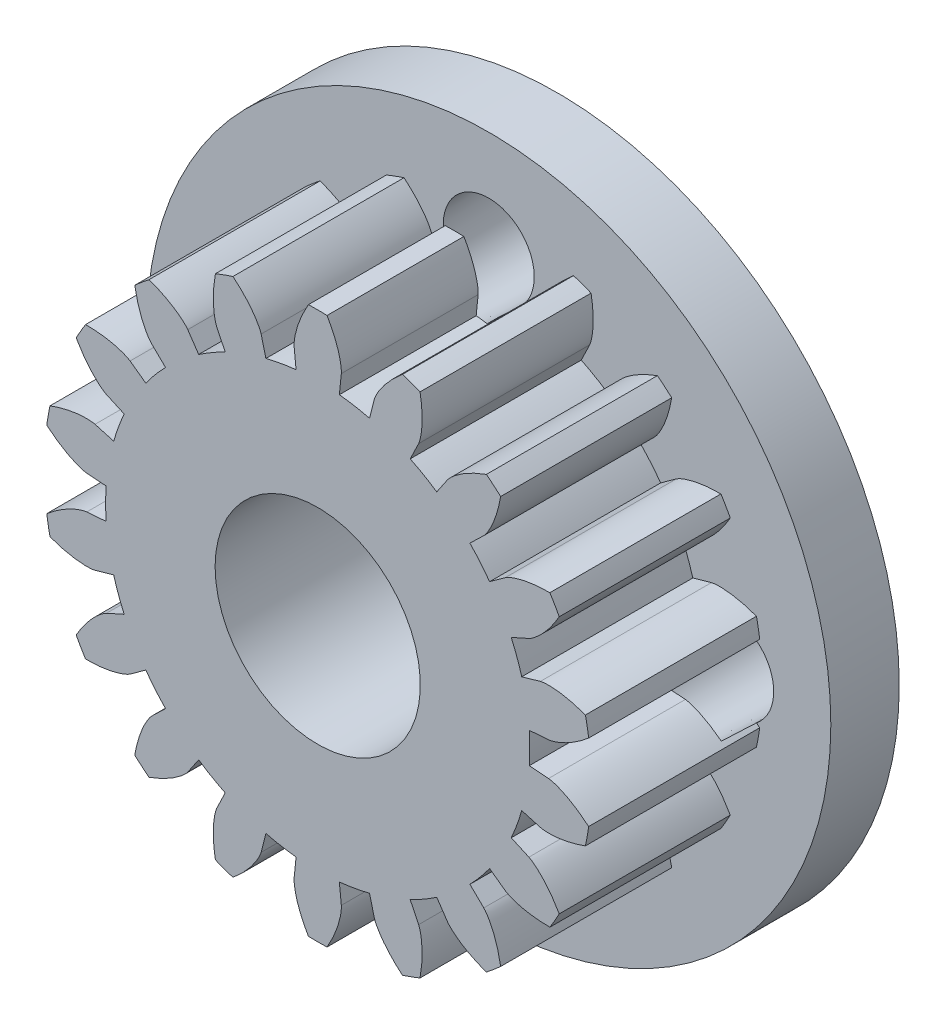
SolidWorks part; units mm, degrees
ref_plane "Front Plane" through (0, 0, 0) normal (0, 0, 1) x (1, 0, 0)
ref_plane "Top Plane" through (0, 0, 0) normal (0, 1, 0) x (1, 0, 0)
ref_plane "Right Plane" through (0, 0, 0) normal (1, 0, 0) x (0, 0, -1)
sketch "Sketch1" plane through (0, 0, 0) normal (0, 0, 1) x (1, 0, 0)
  circle A0 centre (0, 0) radius 10
  dimension "D1" = 20
extrude "Boss-Extrude1" add sketch "Sketch1" along normal blind 2
sketch "Sketch2" plane through (0, 0, 2) normal (0, 0, 1) x (1, 0, 0)
  line L0 (6.749, 0.4894) -> (6.1838, 0.4484)
  line L2 (6.7483, -0.4893) -> (6.1838, -0.4484)
  line L3 (6.5094, -1.8484) -> (5.9642, -1.6936)
  line L4 (6.174, -2.7678) -> (5.6575, -2.5363)
  line L5 (5.4846, -3.9633) -> (5.0253, -3.6313)
  line L6 (4.855, -4.7125) -> (4.4488, -4.3183)
  line L7 (3.7983, -5.6001) -> (3.4802, -5.1311)
  line L8 (2.9504, -6.0888) -> (2.7036, -5.5795)
  line L9 (1.6539, -6.5615) -> (1.5154, -6.012)
  line L10 (0.69, -6.7307) -> (0.6322, -6.1677)
  line L11 (-0.69, -6.7315) -> (-0.6322, -6.1677)
  line L12 (-1.6537, -6.5608) -> (-1.5154, -6.012)
  line L13 (-2.9507, -6.0895) -> (-2.7035, -5.5795)
  line L14 (-3.7979, -5.5995) -> (-3.4802, -5.1311)
  line L15 (-4.8555, -4.7131) -> (-4.4488, -4.3183)
  line L16 (-5.484, -3.9629) -> (-5.0252, -3.6314)
  line L17 (-6.1746, -2.7682) -> (-5.6575, -2.5363)
  line L18 (-6.5087, -1.8483) -> (-5.9642, -1.6936)
  line L19 (-6.749, -0.4894) -> (-6.1838, -0.4484)
  line L20 (-6.7483, 0.4893) -> (-6.1838, 0.4484)
  line L21 (-6.5094, 1.8484) -> (-5.9642, 1.6936)
  line L22 (-6.174, 2.7678) -> (-5.6575, 2.5363)
  line L23 (-5.4846, 3.9633) -> (-5.0253, 3.6313)
  line L24 (-4.855, 4.7125) -> (-4.4488, 4.3183)
  line L25 (-3.7983, 5.6001) -> (-3.4802, 5.1311)
  line L26 (-2.9504, 6.0888) -> (-2.7036, 5.5795)
  line L27 (-1.6539, 6.5615) -> (-1.5154, 6.012)
  line L28 (-0.69, 6.7307) -> (-0.6322, 6.1677)
  line L29 (0.69, 6.7315) -> (0.6322, 6.1677)
  line L30 (1.6537, 6.5608) -> (1.5154, 6.012)
  line L31 (2.9507, 6.0895) -> (2.7035, 5.5795)
  line L32 (3.7979, 5.5995) -> (3.4802, 5.1311)
  line L33 (4.8555, 4.7131) -> (4.4488, 4.3183)
  line L34 (5.484, 3.9629) -> (5.0252, 3.6314)
  line L35 (6.1746, 2.7682) -> (5.6575, 2.5363)
  line L36 (6.5087, 1.8483) -> (5.9642, 1.6936)
  arc A0 (6.1838, -0.4484) -> (6.1838, 0.4484) centre (0, 0) ccw
  arc A1 (6.1838, 0.4484) -> (6.1838, -0.4484) centre (0, 0) ccw construction
  arc A2 (2.9913, 7.4194) -> (2.4781, 7.6062) centre (0, 0) ccw
  arc A3 (5.6575, -2.5363) -> (5.9642, -1.6936) centre (0, 0) ccw
  arc A4 (4.4488, -4.3183) -> (5.0253, -3.6313) centre (0, 0) ccw
  arc A5 (2.7036, -5.5795) -> (3.4802, -5.1311) centre (0, 0) ccw
  arc A6 (0.6322, -6.1677) -> (1.5154, -6.012) centre (0, 0) ccw
  arc A7 (-1.5154, -6.012) -> (-0.6322, -6.1677) centre (0, 0) ccw
  arc A8 (-3.4802, -5.1311) -> (-2.7035, -5.5795) centre (0, 0) ccw
  arc A9 (-5.0252, -3.6314) -> (-4.4488, -4.3183) centre (0, 0) ccw
  arc A10 (-5.9642, -1.6936) -> (-5.6575, -2.5363) centre (0, 0) ccw
  arc A11 (-6.1838, 0.4484) -> (-6.1838, -0.4484) centre (0, 0) ccw
  arc A12 (-5.6575, 2.5363) -> (-5.9642, 1.6936) centre (0, 0) ccw
  arc A13 (-4.4488, 4.3183) -> (-5.0253, 3.6313) centre (0, 0) ccw
  arc A14 (-2.7036, 5.5795) -> (-3.4802, 5.1311) centre (0, 0) ccw
  arc A15 (-0.6322, 6.1677) -> (-1.5154, 6.012) centre (0, 0) ccw
  arc A16 (1.5154, 6.012) -> (0.6322, 6.1677) centre (0, 0) ccw
  arc A17 (3.4802, 5.1311) -> (2.7035, 5.5795) centre (0, 0) ccw
  arc A18 (5.0252, 3.6314) -> (4.4488, 4.3183) centre (0, 0) ccw
  arc A19 (5.9642, 1.6936) -> (5.6575, 2.5363) centre (0, 0) ccw
  arc A20 (4.9301, 6.2999) -> (2.9913, 7.4194) centre (0, 0) ccw construction
  arc A21 (6.7875, 4.2338) -> (5.3484, 5.9489) centre (0, 0) ccw construction
  arc A22 (5.3484, 5.9489) -> (4.9301, 6.2999) centre (0, 0) ccw
  arc A23 (7.8262, 1.657) -> (7.0605, 3.7608) centre (0, 0) ccw construction
  arc A24 (7.0605, 3.7608) -> (6.7875, 4.2338) centre (0, 0) ccw
  arc A25 (7.9209, -1.1196) -> (7.921, 1.1192) centre (0, 0) ccw construction
  arc A26 (7.921, 1.1192) -> (7.8262, 1.657) centre (0, 0) ccw
  arc A27 (7.0603, -3.7612) -> (7.8261, -1.6575) centre (0, 0) ccw construction
  arc A28 (7.8261, -1.6575) -> (7.9209, -1.1196) centre (0, 0) ccw
  arc A29 (5.3481, -5.9492) -> (6.7872, -4.2342) centre (0, 0) ccw construction
  arc A30 (6.7872, -4.2342) -> (7.0603, -3.7612) centre (0, 0) ccw
  arc A31 (2.9908, -7.4196) -> (4.9297, -6.3002) centre (0, 0) ccw construction
  arc A32 (4.9297, -6.3002) -> (5.3481, -5.9492) centre (0, 0) ccw
  arc A33 (0.2728, -7.995) -> (2.4776, -7.6063) centre (0, 0) ccw construction
  arc A34 (2.4776, -7.6063) -> (2.9908, -7.4196) centre (0, 0) ccw
  arc A35 (-2.4781, -7.6062) -> (-0.2733, -7.995) centre (0, 0) ccw construction
  arc A36 (-0.2733, -7.995) -> (0.2728, -7.995) centre (0, 0) ccw
  arc A37 (-4.9301, -6.2999) -> (-2.9913, -7.4194) centre (0, 0) ccw construction
  arc A38 (-2.9913, -7.4194) -> (-2.4781, -7.6062) centre (0, 0) ccw
  arc A39 (-6.7875, -4.2338) -> (-5.3484, -5.9489) centre (0, 0) ccw construction
  arc A40 (-5.3484, -5.9489) -> (-4.9301, -6.2999) centre (0, 0) ccw
  arc A41 (-7.8262, -1.657) -> (-7.0605, -3.7608) centre (0, 0) ccw construction
  arc A42 (-7.0605, -3.7608) -> (-6.7875, -4.2338) centre (0, 0) ccw
  arc A43 (-7.9209, 1.1196) -> (-7.921, -1.1192) centre (0, 0) ccw construction
  arc A44 (-7.921, -1.1192) -> (-7.8262, -1.657) centre (0, 0) ccw
  arc A45 (-7.0603, 3.7612) -> (-7.8261, 1.6575) centre (0, 0) ccw construction
  arc A46 (-7.8261, 1.6575) -> (-7.9209, 1.1196) centre (0, 0) ccw
  arc A47 (-5.3481, 5.9492) -> (-6.7872, 4.2342) centre (0, 0) ccw construction
  arc A48 (-6.7872, 4.2342) -> (-7.0603, 3.7612) centre (0, 0) ccw
  arc A49 (-2.9908, 7.4196) -> (-4.9297, 6.3002) centre (0, 0) ccw construction
  arc A50 (-4.9297, 6.3002) -> (-5.3481, 5.9492) centre (0, 0) ccw
  arc A51 (-0.2728, 7.995) -> (-2.4776, 7.6063) centre (0, 0) ccw construction
  arc A52 (-2.4776, 7.6063) -> (-2.9908, 7.4196) centre (0, 0) ccw
  arc A53 (2.4781, 7.6062) -> (0.2733, 7.995) centre (0, 0) ccw construction
  arc A54 (0.2733, 7.995) -> (-0.2728, 7.995) centre (0, 0) ccw
  spline S0 degree 4 poles (6.749, 0.4894) (6.7546, 0.4899) (6.765, 0.4912) (6.7821, 0.4939) (6.8156, 0.5002) (6.8532, 0.5091) (6.8954, 0.5207) (6.9405, 0.5347) (6.9788, 0.5477) (7.0169, 0.5615) (7.0547, 0.5761) (7.1002, 0.5948) (7.1544, 0.6185) (7.2173, 0.6482) (7.288, 0.6841) (7.3594, 0.7231) (7.429, 0.7635) (7.4986, 0.8065) (7.5654, 0.8498) (7.6341, 0.897) (7.697, 0.9417) (7.7666, 0.9943) (7.8225, 1.0375) (7.8951, 1.0972) (7.9377, 1.1332) (7.9872, 1.1762) (8.009, 1.1958) (8.0224, 1.2079) knots 0 0 0 0 0 0.015084 0.028532 0.04661 0.092111 0.119476 0.146842 0.174209 0.201575 0.228941 0.256307 0.307035 0.361767 0.4165 0.471232 0.525964 0.580697 0.635429 0.690161 0.744894 0.799626 0.854358 0.909091 0.954545 1 1 1 1 1 construction
  spline S1 degree 4 poles (6.749, 0.4894) (6.7546, 0.4899) (6.765, 0.4912) (6.7821, 0.4939) (6.8156, 0.5002) (6.8532, 0.5091) (6.8954, 0.5207) (6.9405, 0.5347) (6.9788, 0.5477) (7.0169, 0.5615) (7.0547, 0.5761) (7.1002, 0.5948) (7.1544, 0.6185) (7.2173, 0.6482) (7.288, 0.6841) (7.3594, 0.7231) (7.429, 0.7635) (7.4986, 0.8065) (7.5654, 0.8498) (7.6341, 0.897) (7.697, 0.9417) (7.7666, 0.9943) (7.8225, 1.0375) (7.8794, 1.0842) (7.907, 1.1073) (7.921, 1.1192) knots 0 0 0 0 0 0.015084 0.028532 0.04661 0.092111 0.119476 0.146842 0.174209 0.201575 0.228941 0.256307 0.307035 0.361767 0.4165 0.471232 0.525964 0.580697 0.635429 0.690161 0.744894 0.799626 0.854358 0.909091 0.909091 0.909091 0.909091 0.909091
  spline S2 degree 4 poles (6.7483, -0.4893) (6.7539, -0.4898) (6.7643, -0.4911) (6.7814, -0.4938) (6.8149, -0.5002) (6.8525, -0.509) (6.8948, -0.5206) (6.9399, -0.5346) (6.9783, -0.5476) (7.0164, -0.5615) (7.0541, -0.5761) (7.0997, -0.5948) (7.1539, -0.6185) (7.2169, -0.6482) (7.2876, -0.6841) (7.359, -0.7232) (7.4287, -0.7636) (7.4983, -0.8067) (7.5652, -0.85) (7.6339, -0.8972) (7.6968, -0.942) (7.7664, -0.9947) (7.8224, -1.0379) (7.8951, -1.0976) (7.9377, -1.1337) (7.9872, -1.1767) (8.009, -1.1963) (8.0224, -1.2084) knots 0 0 0 0 0 0.015084 0.028532 0.04661 0.092111 0.119476 0.146842 0.174209 0.201575 0.228941 0.256307 0.307035 0.361767 0.4165 0.471232 0.525964 0.580697 0.635429 0.690161 0.744894 0.799626 0.854358 0.909091 0.954545 1 1 1 1 1 construction
  spline S3 degree 4 poles (6.7483, -0.4893) (6.7539, -0.4898) (6.7643, -0.4911) (6.7814, -0.4938) (6.8149, -0.5002) (6.8525, -0.509) (6.8948, -0.5206) (6.9399, -0.5346) (6.9783, -0.5476) (7.0164, -0.5615) (7.0541, -0.5761) (7.0997, -0.5948) (7.1539, -0.6185) (7.2169, -0.6482) (7.2876, -0.6841) (7.359, -0.7232) (7.4287, -0.7636) (7.4983, -0.8067) (7.5652, -0.85) (7.6339, -0.8972) (7.6968, -0.942) (7.7664, -0.9947) (7.8224, -1.0379) (7.8793, -1.0847) (7.9069, -1.1077) (7.9209, -1.1196) knots 0 0 0 0 0 0.015084 0.028532 0.04661 0.092111 0.119476 0.146842 0.174209 0.201575 0.228941 0.256307 0.307035 0.361767 0.4165 0.471232 0.525964 0.580697 0.635429 0.690161 0.744894 0.799626 0.854358 0.909091 0.909091 0.909091 0.909091 0.909091
  spline S4 degree 4 poles (6.5094, -1.8484) (6.5148, -1.8499) (6.5251, -1.8522) (6.542, -1.8555) (6.5756, -1.861) (6.614, -1.8655) (6.6576, -1.8691) (6.7048, -1.8713) (6.7453, -1.8723) (6.7858, -1.8723) (6.8263, -1.8715) (6.8754, -1.8695) (6.9345, -1.8657) (7.0037, -1.8594) (7.0825, -1.8498) (7.1629, -1.8376) (7.2421, -1.8234) (7.3222, -1.8068) (7.3998, -1.789) (7.4805, -1.7681) (7.5549, -1.7476) (7.6383, -1.722) (7.7056, -1.7005) (7.7943, -1.6693) (7.8466, -1.65) (7.9078, -1.6265) (7.935, -1.6155) (7.9517, -1.6088) knots 0 0 0 0 0 0.015084 0.028532 0.04661 0.092111 0.119476 0.146842 0.174209 0.201575 0.228941 0.256307 0.307035 0.361767 0.4165 0.471232 0.525964 0.580697 0.635429 0.690161 0.744894 0.799626 0.854358 0.909091 0.954545 1 1 1 1 1 construction
  spline S5 degree 4 poles (6.5094, -1.8484) (6.5148, -1.8499) (6.5251, -1.8522) (6.542, -1.8555) (6.5756, -1.861) (6.614, -1.8655) (6.6576, -1.8691) (6.7048, -1.8713) (6.7453, -1.8723) (6.7858, -1.8723) (6.8263, -1.8715) (6.8754, -1.8695) (6.9345, -1.8657) (7.0037, -1.8594) (7.0825, -1.8498) (7.1629, -1.8376) (7.2421, -1.8234) (7.3222, -1.8068) (7.3998, -1.789) (7.4805, -1.7681) (7.5549, -1.7476) (7.6383, -1.722) (7.7056, -1.7005) (7.775, -1.676) (7.8088, -1.6638) (7.8261, -1.6575) knots 0 0 0 0 0 0.015084 0.028532 0.04661 0.092111 0.119476 0.146842 0.174209 0.201575 0.228941 0.256307 0.307035 0.361767 0.4165 0.471232 0.525964 0.580697 0.635429 0.690161 0.744894 0.799626 0.854358 0.909091 0.909091 0.909091 0.909091 0.909091
  spline S6 degree 4 poles (6.174, -2.7678) (6.179, -2.7702) (6.1884, -2.775) (6.2036, -2.7834) (6.2328, -2.8008) (6.2652, -2.822) (6.3009, -2.8473) (6.3385, -2.876) (6.3701, -2.9013) (6.4012, -2.9273) (6.4317, -2.954) (6.4681, -2.9871) (6.511, -3.028) (6.5599, -3.0774) (6.6141, -3.1354) (6.6679, -3.1965) (6.7195, -3.2583) (6.7702, -3.3226) (6.8183, -3.3862) (6.8666, -3.454) (6.9105, -3.5177) (6.9579, -3.591) (6.9956, -3.6507) (7.0435, -3.7317) (7.0713, -3.7801) (7.103, -3.8375) (7.1168, -3.8634) (7.1253, -3.8793) knots 0 0 0 0 0 0.015084 0.028532 0.04661 0.092111 0.119476 0.146842 0.174209 0.201575 0.228941 0.256307 0.307035 0.361767 0.4165 0.471232 0.525964 0.580697 0.635429 0.690161 0.744894 0.799626 0.854358 0.909091 0.954545 1 1 1 1 1 construction
  spline S7 degree 4 poles (6.174, -2.7678) (6.179, -2.7702) (6.1884, -2.775) (6.2036, -2.7834) (6.2328, -2.8008) (6.2652, -2.822) (6.3009, -2.8473) (6.3385, -2.876) (6.3701, -2.9013) (6.4012, -2.9273) (6.4317, -2.954) (6.4681, -2.9871) (6.511, -3.028) (6.5599, -3.0774) (6.6141, -3.1354) (6.6679, -3.1965) (6.7195, -3.2583) (6.7702, -3.3226) (6.8183, -3.3862) (6.8666, -3.454) (6.9105, -3.5177) (6.9579, -3.591) (6.9956, -3.6507) (7.0331, -3.7141) (7.0512, -3.7452) (7.0603, -3.7612) knots 0 0 0 0 0 0.015084 0.028532 0.04661 0.092111 0.119476 0.146842 0.174209 0.201575 0.228941 0.256307 0.307035 0.361767 0.4165 0.471232 0.525964 0.580697 0.635429 0.690161 0.744894 0.799626 0.854358 0.909091 0.909091 0.909091 0.909091 0.909091
  spline S8 degree 4 poles (5.4846, -3.9633) (5.4892, -3.9665) (5.4981, -3.9722) (5.5128, -3.9811) (5.5426, -3.9978) (5.5771, -4.0152) (5.6169, -4.0334) (5.6604, -4.0517) (5.6981, -4.0664) (5.7362, -4.0802) (5.7745, -4.0933) (5.8214, -4.1083) (5.8782, -4.125) (5.9454, -4.1427) (6.0226, -4.1606) (6.1024, -4.1766) (6.1817, -4.1904) (6.2627, -4.2022) (6.3417, -4.212) (6.4246, -4.22) (6.5016, -4.2261) (6.5887, -4.2306) (6.6593, -4.2334) (6.7533, -4.2344) (6.8091, -4.2342) (6.8746, -4.233) (6.9039, -4.232) (6.9219, -4.2314) knots 0 0 0 0 0 0.015084 0.028532 0.04661 0.092111 0.119476 0.146842 0.174209 0.201575 0.228941 0.256307 0.307035 0.361767 0.4165 0.471232 0.525964 0.580697 0.635429 0.690161 0.744894 0.799626 0.854358 0.909091 0.954545 1 1 1 1 1 construction
  spline S9 degree 4 poles (5.4846, -3.9633) (5.4892, -3.9665) (5.4981, -3.9722) (5.5128, -3.9811) (5.5426, -3.9978) (5.5771, -4.0152) (5.6169, -4.0334) (5.6604, -4.0517) (5.6981, -4.0664) (5.7362, -4.0802) (5.7745, -4.0933) (5.8214, -4.1083) (5.8782, -4.125) (5.9454, -4.1427) (6.0226, -4.1606) (6.1024, -4.1766) (6.1817, -4.1904) (6.2627, -4.2022) (6.3417, -4.212) (6.4246, -4.22) (6.5016, -4.2261) (6.5887, -4.2306) (6.6593, -4.2334) (6.7329, -4.2342) (6.7688, -4.2343) (6.7872, -4.2342) knots 0 0 0 0 0 0.015084 0.028532 0.04661 0.092111 0.119476 0.146842 0.174209 0.201575 0.228941 0.256307 0.307035 0.361767 0.4165 0.471232 0.525964 0.580697 0.635429 0.690161 0.744894 0.799626 0.854358 0.909091 0.909091 0.909091 0.909091 0.909091
  spline S10 degree 4 poles (4.855, -4.7125) (4.8589, -4.7165) (4.8661, -4.7243) (4.8775, -4.7372) (4.899, -4.7637) (4.9222, -4.7946) (4.9471, -4.8307) (4.9726, -4.8704) (4.9937, -4.905) (5.0139, -4.9401) (5.0335, -4.9756) (5.0563, -5.0192) (5.0827, -5.0723) (5.1118, -5.1355) (5.1429, -5.2085) (5.1725, -5.2843) (5.1999, -5.36) (5.2255, -5.4378) (5.2489, -5.5139) (5.2712, -5.5943) (5.2906, -5.669) (5.3101, -5.7541) (5.3251, -5.8232) (5.3424, -5.9157) (5.3519, -5.9707) (5.3622, -6.0355) (5.3662, -6.0645) (5.3688, -6.0824) knots 0 0 0 0 0 0.015084 0.028532 0.04661 0.092111 0.119476 0.146842 0.174209 0.201575 0.228941 0.256307 0.307035 0.361767 0.4165 0.471232 0.525964 0.580697 0.635429 0.690161 0.744894 0.799626 0.854358 0.909091 0.954545 1 1 1 1 1 construction
  spline S11 degree 4 poles (4.855, -4.7125) (4.8589, -4.7165) (4.8661, -4.7243) (4.8775, -4.7372) (4.899, -4.7637) (4.9222, -4.7946) (4.9471, -4.8307) (4.9726, -4.8704) (4.9937, -4.905) (5.0139, -4.9401) (5.0335, -4.9756) (5.0563, -5.0192) (5.0827, -5.0723) (5.1118, -5.1355) (5.1429, -5.2085) (5.1725, -5.2843) (5.1999, -5.36) (5.2255, -5.4378) (5.2489, -5.5139) (5.2712, -5.5943) (5.2906, -5.669) (5.3101, -5.7541) (5.3251, -5.8232) (5.3387, -5.8956) (5.345, -5.931) (5.3481, -5.9492) knots 0 0 0 0 0 0.015084 0.028532 0.04661 0.092111 0.119476 0.146842 0.174209 0.201575 0.228941 0.256307 0.307035 0.361767 0.4165 0.471232 0.525964 0.580697 0.635429 0.690161 0.744894 0.799626 0.854358 0.909091 0.909091 0.909091 0.909091 0.909091
  spline S12 degree 4 poles (3.7983, -5.6001) (3.8015, -5.6047) (3.8079, -5.6131) (3.8187, -5.6265) (3.841, -5.6523) (3.8675, -5.6805) (3.8986, -5.7113) (3.9333, -5.7433) (3.9637, -5.77) (3.9947, -5.7961) (4.0263, -5.8215) (4.0652, -5.8515) (4.1128, -5.8866) (4.17, -5.9263) (4.2364, -5.9696) (4.3059, -6.0119) (4.3757, -6.052) (4.4478, -6.0907) (4.5186, -6.127) (4.5938, -6.1628) (4.664, -6.1949) (4.7444, -6.2289) (4.8098, -6.2557) (4.8978, -6.2888) (4.9502, -6.3077) (5.0123, -6.329) (5.0401, -6.3381) (5.0573, -6.3437) knots 0 0 0 0 0 0.015084 0.028532 0.04661 0.092111 0.119476 0.146842 0.174209 0.201575 0.228941 0.256307 0.307035 0.361767 0.4165 0.471232 0.525964 0.580697 0.635429 0.690161 0.744894 0.799626 0.854358 0.909091 0.954545 1 1 1 1 1 construction
  spline S13 degree 4 poles (3.7983, -5.6001) (3.8015, -5.6047) (3.8079, -5.6131) (3.8187, -5.6265) (3.841, -5.6523) (3.8675, -5.6805) (3.8986, -5.7113) (3.9333, -5.7433) (3.9637, -5.77) (3.9947, -5.7961) (4.0263, -5.8215) (4.0652, -5.8515) (4.1128, -5.8866) (4.17, -5.9263) (4.2364, -5.9696) (4.3059, -6.0119) (4.3757, -6.052) (4.4478, -6.0907) (4.5186, -6.127) (4.5938, -6.1628) (4.664, -6.1949) (4.7444, -6.2289) (4.8098, -6.2557) (4.8787, -6.2816) (4.9124, -6.294) (4.9297, -6.3002) knots 0 0 0 0 0 0.015084 0.028532 0.04661 0.092111 0.119476 0.146842 0.174209 0.201575 0.228941 0.256307 0.307035 0.361767 0.4165 0.471232 0.525964 0.580697 0.635429 0.690161 0.744894 0.799626 0.854358 0.909091 0.909091 0.909091 0.909091 0.909091
  spline S14 degree 4 poles (2.9504, -6.0888) (2.9528, -6.0939) (2.9569, -6.1037) (2.9631, -6.1197) (2.9743, -6.152) (2.9855, -6.189) (2.9965, -6.2313) (3.0069, -6.2774) (3.0149, -6.3172) (3.0219, -6.3571) (3.0282, -6.3971) (3.0347, -6.4459) (3.0413, -6.5047) (3.0471, -6.5741) (3.0513, -6.6533) (3.0532, -6.7347) (3.053, -6.8152) (3.0506, -6.8971) (3.0465, -6.9766) (3.0399, -7.0597) (3.0326, -7.1366) (3.0218, -7.2233) (3.0123, -7.2933) (2.997, -7.3861) (2.9871, -7.4411) (2.9745, -7.5055) (2.9684, -7.5342) (2.9647, -7.5518) knots 0 0 0 0 0 0.015084 0.028532 0.04661 0.092111 0.119476 0.146842 0.174209 0.201575 0.228941 0.256307 0.307035 0.361767 0.4165 0.471232 0.525964 0.580697 0.635429 0.690161 0.744894 0.799626 0.854358 0.909091 0.954545 1 1 1 1 1 construction
  spline S15 degree 4 poles (2.9504, -6.0888) (2.9528, -6.0939) (2.9569, -6.1037) (2.9631, -6.1197) (2.9743, -6.152) (2.9855, -6.189) (2.9965, -6.2313) (3.0069, -6.2774) (3.0149, -6.3172) (3.0219, -6.3571) (3.0282, -6.3971) (3.0347, -6.4459) (3.0413, -6.5047) (3.0471, -6.5741) (3.0513, -6.6533) (3.0532, -6.7347) (3.053, -6.8152) (3.0506, -6.8971) (3.0465, -6.9766) (3.0399, -7.0597) (3.0326, -7.1366) (3.0218, -7.2233) (3.0123, -7.2933) (3.0003, -7.366) (2.9941, -7.4014) (2.9908, -7.4196) knots 0 0 0 0 0 0.015084 0.028532 0.04661 0.092111 0.119476 0.146842 0.174209 0.201575 0.228941 0.256307 0.307035 0.361767 0.4165 0.471232 0.525964 0.580697 0.635429 0.690161 0.744894 0.799626 0.854358 0.909091 0.909091 0.909091 0.909091 0.909091
  spline S16 degree 4 poles (1.6539, -6.5615) (1.6554, -6.5669) (1.6585, -6.577) (1.664, -6.5933) (1.6762, -6.6252) (1.6914, -6.6607) (1.7101, -6.7002) (1.7318, -6.7422) (1.7512, -6.7777) (1.7714, -6.8128) (1.7924, -6.8474) (1.8187, -6.889) (1.8515, -6.9383) (1.8916, -6.9951) (1.9392, -7.0585) (1.99, -7.122) (2.0419, -7.1836) (2.0964, -7.2446) (2.1506, -7.3029) (2.209, -7.3623) (2.264, -7.4165) (2.3279, -7.4759) (2.3801, -7.5235) (2.4515, -7.5847) (2.4943, -7.6204) (2.5453, -7.6616) (2.5684, -7.6797) (2.5826, -7.6908) knots 0 0 0 0 0 0.015084 0.028532 0.04661 0.092111 0.119476 0.146842 0.174209 0.201575 0.228941 0.256307 0.307035 0.361767 0.4165 0.471232 0.525964 0.580697 0.635429 0.690161 0.744894 0.799626 0.854358 0.909091 0.954545 1 1 1 1 1 construction
  spline S17 degree 4 poles (1.6539, -6.5615) (1.6554, -6.5669) (1.6585, -6.577) (1.664, -6.5933) (1.6762, -6.6252) (1.6914, -6.6607) (1.7101, -6.7002) (1.7318, -6.7422) (1.7512, -6.7777) (1.7714, -6.8128) (1.7924, -6.8474) (1.8187, -6.889) (1.8515, -6.9383) (1.8916, -6.9951) (1.9392, -7.0585) (1.99, -7.122) (2.0419, -7.1836) (2.0964, -7.2446) (2.1506, -7.3029) (2.209, -7.3623) (2.264, -7.4165) (2.3279, -7.4759) (2.3801, -7.5235) (2.436, -7.5714) (2.4635, -7.5946) (2.4776, -7.6063) knots 0 0 0 0 0 0.015084 0.028532 0.04661 0.092111 0.119476 0.146842 0.174209 0.201575 0.228941 0.256307 0.307035 0.361767 0.4165 0.471232 0.525964 0.580697 0.635429 0.690161 0.744894 0.799626 0.854358 0.909091 0.909091 0.909091 0.909091 0.909091
  spline S18 degree 4 poles (0.69, -6.7307) (0.6905, -6.7363) (0.691, -6.7469) (0.6913, -6.7641) (0.6908, -6.7982) (0.6887, -6.8368) (0.6846, -6.8804) (0.6786, -6.9273) (0.6725, -6.9673) (0.6654, -7.0073) (0.6576, -7.047) (0.6471, -7.0951) (0.6332, -7.1527) (0.6148, -7.2198) (0.5917, -7.2957) (0.5657, -7.3728) (0.538, -7.4484) (0.5076, -7.5245) (0.4766, -7.5979) (0.442, -7.6737) (0.4088, -7.7435) (0.3691, -7.8212) (0.3362, -7.8837) (0.29, -7.9657) (0.2619, -8.0139) (0.2281, -8.0702) (0.2126, -8.0951) (0.203, -8.1104) knots 0 0 0 0 0 0.015084 0.028532 0.04661 0.092111 0.119476 0.146842 0.174209 0.201575 0.228941 0.256307 0.307035 0.361767 0.4165 0.471232 0.525964 0.580697 0.635429 0.690161 0.744894 0.799626 0.854358 0.909091 0.954545 1 1 1 1 1 construction
  spline S19 degree 4 poles (0.69, -6.7307) (0.6905, -6.7363) (0.691, -6.7469) (0.6913, -6.7641) (0.6908, -6.7982) (0.6887, -6.8368) (0.6846, -6.8804) (0.6786, -6.9273) (0.6725, -6.9673) (0.6654, -7.0073) (0.6576, -7.047) (0.6471, -7.0951) (0.6332, -7.1527) (0.6148, -7.2198) (0.5917, -7.2957) (0.5657, -7.3728) (0.538, -7.4484) (0.5076, -7.5245) (0.4766, -7.5979) (0.442, -7.6737) (0.4088, -7.7435) (0.3691, -7.8212) (0.3362, -7.8837) (0.3, -7.9479) (0.2821, -7.9791) (0.2728, -7.995) knots 0 0 0 0 0 0.015084 0.028532 0.04661 0.092111 0.119476 0.146842 0.174209 0.201575 0.228941 0.256307 0.307035 0.361767 0.4165 0.471232 0.525964 0.580697 0.635429 0.690161 0.744894 0.799626 0.854358 0.909091 0.909091 0.909091 0.909091 0.909091
  spline S20 degree 4 poles (-0.69, -6.7315) (-0.6905, -6.737) (-0.691, -6.7476) (-0.6913, -6.7648) (-0.6909, -6.7989) (-0.6887, -6.8375) (-0.6846, -6.8811) (-0.6786, -6.9279) (-0.6725, -6.9679) (-0.6655, -7.0078) (-0.6577, -7.0475) (-0.6472, -7.0956) (-0.6332, -7.1531) (-0.615, -7.2202) (-0.5919, -7.2961) (-0.5658, -7.3731) (-0.5382, -7.4487) (-0.5079, -7.5247) (-0.4769, -7.5981) (-0.4423, -7.6738) (-0.4092, -7.7436) (-0.3694, -7.8213) (-0.3366, -7.8838) (-0.2905, -7.9657) (-0.2624, -8.0139) (-0.2286, -8.0701) (-0.2131, -8.095) (-0.2036, -8.1103) knots 0 0 0 0 0 0.015084 0.028532 0.04661 0.092111 0.119476 0.146842 0.174209 0.201575 0.228941 0.256307 0.307035 0.361767 0.4165 0.471232 0.525964 0.580697 0.635429 0.690161 0.744894 0.799626 0.854358 0.909091 0.954545 1 1 1 1 1 construction
  spline S21 degree 4 poles (-0.69, -6.7315) (-0.6905, -6.737) (-0.691, -6.7476) (-0.6913, -6.7648) (-0.6909, -6.7989) (-0.6887, -6.8375) (-0.6846, -6.8811) (-0.6786, -6.9279) (-0.6725, -6.9679) (-0.6655, -7.0078) (-0.6577, -7.0475) (-0.6472, -7.0956) (-0.6332, -7.1531) (-0.615, -7.2202) (-0.5919, -7.2961) (-0.5658, -7.3731) (-0.5382, -7.4487) (-0.5079, -7.5247) (-0.4769, -7.5981) (-0.4423, -7.6738) (-0.4092, -7.7436) (-0.3694, -7.8213) (-0.3366, -7.8838) (-0.3005, -7.9479) (-0.2826, -7.9791) (-0.2733, -7.995) knots 0 0 0 0 0 0.015084 0.028532 0.04661 0.092111 0.119476 0.146842 0.174209 0.201575 0.228941 0.256307 0.307035 0.361767 0.4165 0.471232 0.525964 0.580697 0.635429 0.690161 0.744894 0.799626 0.854358 0.909091 0.909091 0.909091 0.909091 0.909091
  spline S22 degree 4 poles (-1.6537, -6.5608) (-1.6551, -6.5662) (-1.6583, -6.5763) (-1.6638, -6.5926) (-1.6759, -6.6245) (-1.6912, -6.66) (-1.7099, -6.6996) (-1.7316, -6.7416) (-1.7511, -6.7772) (-1.7713, -6.8123) (-1.7923, -6.8469) (-1.8186, -6.8885) (-1.8514, -6.9378) (-1.8915, -6.9947) (-1.9392, -7.0581) (-1.9901, -7.1216) (-2.042, -7.1832) (-2.0965, -7.2443) (-2.1507, -7.3027) (-2.2092, -7.3621) (-2.2642, -7.4163) (-2.3282, -7.4757) (-2.3805, -7.5233) (-2.4519, -7.5845) (-2.4948, -7.6202) (-2.5458, -7.6615) (-2.5689, -7.6796) (-2.5831, -7.6907) knots 0 0 0 0 0 0.015084 0.028532 0.04661 0.092111 0.119476 0.146842 0.174209 0.201575 0.228941 0.256307 0.307035 0.361767 0.4165 0.471232 0.525964 0.580697 0.635429 0.690161 0.744894 0.799626 0.854358 0.909091 0.954545 1 1 1 1 1 construction
  spline S23 degree 4 poles (-1.6537, -6.5608) (-1.6551, -6.5662) (-1.6583, -6.5763) (-1.6638, -6.5926) (-1.6759, -6.6245) (-1.6912, -6.66) (-1.7099, -6.6996) (-1.7316, -6.7416) (-1.7511, -6.7772) (-1.7713, -6.8123) (-1.7923, -6.8469) (-1.8186, -6.8885) (-1.8514, -6.9378) (-1.8915, -6.9947) (-1.9392, -7.0581) (-1.9901, -7.1216) (-2.042, -7.1832) (-2.0965, -7.2443) (-2.1507, -7.3027) (-2.2092, -7.3621) (-2.2642, -7.4163) (-2.3282, -7.4757) (-2.3805, -7.5233) (-2.4364, -7.5712) (-2.4639, -7.5944) (-2.4781, -7.6062) knots 0 0 0 0 0 0.015084 0.028532 0.04661 0.092111 0.119476 0.146842 0.174209 0.201575 0.228941 0.256307 0.307035 0.361767 0.4165 0.471232 0.525964 0.580697 0.635429 0.690161 0.744894 0.799626 0.854358 0.909091 0.909091 0.909091 0.909091 0.909091
  spline S24 degree 4 poles (-2.9507, -6.0895) (-2.953, -6.0946) (-2.9571, -6.1043) (-2.9634, -6.1204) (-2.9746, -6.1526) (-2.9857, -6.1896) (-2.9968, -6.2319) (-3.0072, -6.278) (-3.0151, -6.3177) (-3.0222, -6.3576) (-3.0284, -6.3976) (-3.035, -6.4463) (-3.0416, -6.5051) (-3.0473, -6.5744) (-3.0516, -6.6536) (-3.0535, -6.7349) (-3.0533, -6.8154) (-3.0508, -6.8972) (-3.0468, -6.9767) (-3.0402, -7.0598) (-3.033, -7.1367) (-3.0222, -7.2232) (-3.0127, -7.2932) (-2.9974, -7.386) (-2.9875, -7.4409) (-2.975, -7.5053) (-2.9689, -7.5339) (-2.9652, -7.5516) knots 0 0 0 0 0 0.015084 0.028532 0.04661 0.092111 0.119476 0.146842 0.174209 0.201575 0.228941 0.256307 0.307035 0.361767 0.4165 0.471232 0.525964 0.580697 0.635429 0.690161 0.744894 0.799626 0.854358 0.909091 0.954545 1 1 1 1 1 construction
  spline S25 degree 4 poles (-2.9507, -6.0895) (-2.953, -6.0946) (-2.9571, -6.1043) (-2.9634, -6.1204) (-2.9746, -6.1526) (-2.9857, -6.1896) (-2.9968, -6.2319) (-3.0072, -6.278) (-3.0151, -6.3177) (-3.0222, -6.3576) (-3.0284, -6.3976) (-3.035, -6.4463) (-3.0416, -6.5051) (-3.0473, -6.5744) (-3.0516, -6.6536) (-3.0535, -6.7349) (-3.0533, -6.8154) (-3.0508, -6.8972) (-3.0468, -6.9767) (-3.0402, -7.0598) (-3.033, -7.1367) (-3.0222, -7.2232) (-3.0127, -7.2932) (-3.0007, -7.3659) (-2.9945, -7.4013) (-2.9913, -7.4194) knots 0 0 0 0 0 0.015084 0.028532 0.04661 0.092111 0.119476 0.146842 0.174209 0.201575 0.228941 0.256307 0.307035 0.361767 0.4165 0.471232 0.525964 0.580697 0.635429 0.690161 0.744894 0.799626 0.854358 0.909091 0.909091 0.909091 0.909091 0.909091
  spline S26 degree 4 poles (-3.7979, -5.5995) (-3.8011, -5.6041) (-3.8075, -5.6125) (-3.8183, -5.626) (-3.8406, -5.6518) (-3.8671, -5.68) (-3.8982, -5.7108) (-3.9329, -5.7428) (-3.9634, -5.7696) (-3.9944, -5.7956) (-4.026, -5.821) (-4.0649, -5.8511) (-4.1126, -5.8862) (-4.1698, -5.9259) (-4.2363, -5.9692) (-4.3058, -6.0115) (-4.3756, -6.0516) (-4.4478, -6.0904) (-4.5187, -6.1267) (-4.5939, -6.1625) (-4.6642, -6.1946) (-4.7446, -6.2286) (-4.81, -6.2554) (-4.8981, -6.2885) (-4.9506, -6.3074) (-5.0127, -6.3287) (-5.0406, -6.3378) (-5.0577, -6.3434) knots 0 0 0 0 0 0.015084 0.028532 0.04661 0.092111 0.119476 0.146842 0.174209 0.201575 0.228941 0.256307 0.307035 0.361767 0.4165 0.471232 0.525964 0.580697 0.635429 0.690161 0.744894 0.799626 0.854358 0.909091 0.954545 1 1 1 1 1 construction
  spline S27 degree 4 poles (-3.7979, -5.5995) (-3.8011, -5.6041) (-3.8075, -5.6125) (-3.8183, -5.626) (-3.8406, -5.6518) (-3.8671, -5.68) (-3.8982, -5.7108) (-3.9329, -5.7428) (-3.9634, -5.7696) (-3.9944, -5.7956) (-4.026, -5.821) (-4.0649, -5.8511) (-4.1126, -5.8862) (-4.1698, -5.9259) (-4.2363, -5.9692) (-4.3058, -6.0115) (-4.3756, -6.0516) (-4.4478, -6.0904) (-4.5187, -6.1267) (-4.5939, -6.1625) (-4.6642, -6.1946) (-4.7446, -6.2286) (-4.81, -6.2554) (-4.879, -6.2813) (-4.9128, -6.2937) (-4.9301, -6.2999) knots 0 0 0 0 0 0.015084 0.028532 0.04661 0.092111 0.119476 0.146842 0.174209 0.201575 0.228941 0.256307 0.307035 0.361767 0.4165 0.471232 0.525964 0.580697 0.635429 0.690161 0.744894 0.799626 0.854358 0.909091 0.909091 0.909091 0.909091 0.909091
  spline S28 degree 4 poles (-4.8555, -4.7131) (-4.8594, -4.717) (-4.8666, -4.7248) (-4.8779, -4.7378) (-4.8995, -4.7642) (-4.9226, -4.7951) (-4.9475, -4.8311) (-4.973, -4.8709) (-4.9941, -4.9054) (-5.0143, -4.9405) (-5.0339, -4.976) (-5.0567, -5.0195) (-5.083, -5.0726) (-5.1121, -5.1357) (-5.1432, -5.2087) (-5.1728, -5.2844) (-5.2002, -5.3601) (-5.2259, -5.4378) (-5.2493, -5.5139) (-5.2715, -5.5942) (-5.2909, -5.6689) (-5.3104, -5.754) (-5.3254, -5.823) (-5.3428, -5.9154) (-5.3523, -5.9704) (-5.3625, -6.0351) (-5.3666, -6.0641) (-5.3691, -6.082) knots 0 0 0 0 0 0.015084 0.028532 0.04661 0.092111 0.119476 0.146842 0.174209 0.201575 0.228941 0.256307 0.307035 0.361767 0.4165 0.471232 0.525964 0.580697 0.635429 0.690161 0.744894 0.799626 0.854358 0.909091 0.954545 1 1 1 1 1 construction
  spline S29 degree 4 poles (-4.8555, -4.7131) (-4.8594, -4.717) (-4.8666, -4.7248) (-4.8779, -4.7378) (-4.8995, -4.7642) (-4.9226, -4.7951) (-4.9475, -4.8311) (-4.973, -4.8709) (-4.9941, -4.9054) (-5.0143, -4.9405) (-5.0339, -4.976) (-5.0567, -5.0195) (-5.083, -5.0726) (-5.1121, -5.1357) (-5.1432, -5.2087) (-5.1728, -5.2844) (-5.2002, -5.3601) (-5.2259, -5.4378) (-5.2493, -5.5139) (-5.2715, -5.5942) (-5.2909, -5.6689) (-5.3104, -5.754) (-5.3254, -5.823) (-5.339, -5.8953) (-5.3453, -5.9307) (-5.3484, -5.9489) knots 0 0 0 0 0 0.015084 0.028532 0.04661 0.092111 0.119476 0.146842 0.174209 0.201575 0.228941 0.256307 0.307035 0.361767 0.4165 0.471232 0.525964 0.580697 0.635429 0.690161 0.744894 0.799626 0.854358 0.909091 0.909091 0.909091 0.909091 0.909091
  spline S30 degree 4 poles (-5.484, -3.9629) (-5.4886, -3.9661) (-5.4975, -3.9718) (-5.5122, -3.9808) (-5.542, -3.9974) (-5.5765, -4.0148) (-5.6163, -4.0331) (-5.6599, -4.0513) (-5.6977, -4.0661) (-5.7358, -4.0799) (-5.7741, -4.093) (-5.821, -4.108) (-5.8778, -4.1247) (-5.9451, -4.1424) (-6.0224, -4.1603) (-6.1022, -4.1763) (-6.1815, -4.1901) (-6.2626, -4.2019) (-6.3416, -4.2117) (-6.4246, -4.2196) (-6.5016, -4.2258) (-6.5888, -4.2302) (-6.6594, -4.233) (-6.7535, -4.234) (-6.8093, -4.2338) (-6.8749, -4.2326) (-6.9042, -4.2316) (-6.9223, -4.231) knots 0 0 0 0 0 0.015084 0.028532 0.04661 0.092111 0.119476 0.146842 0.174209 0.201575 0.228941 0.256307 0.307035 0.361767 0.4165 0.471232 0.525964 0.580697 0.635429 0.690161 0.744894 0.799626 0.854358 0.909091 0.954545 1 1 1 1 1 construction
  spline S31 degree 4 poles (-5.484, -3.9629) (-5.4886, -3.9661) (-5.4975, -3.9718) (-5.5122, -3.9808) (-5.542, -3.9974) (-5.5765, -4.0148) (-5.6163, -4.0331) (-5.6599, -4.0513) (-5.6977, -4.0661) (-5.7358, -4.0799) (-5.7741, -4.093) (-5.821, -4.108) (-5.8778, -4.1247) (-5.9451, -4.1424) (-6.0224, -4.1603) (-6.1022, -4.1763) (-6.1815, -4.1901) (-6.2626, -4.2019) (-6.3416, -4.2117) (-6.4246, -4.2196) (-6.5016, -4.2258) (-6.5888, -4.2302) (-6.6594, -4.233) (-6.7331, -4.2338) (-6.7691, -4.2339) (-6.7875, -4.2338) knots 0 0 0 0 0 0.015084 0.028532 0.04661 0.092111 0.119476 0.146842 0.174209 0.201575 0.228941 0.256307 0.307035 0.361767 0.4165 0.471232 0.525964 0.580697 0.635429 0.690161 0.744894 0.799626 0.854358 0.909091 0.909091 0.909091 0.909091 0.909091
  spline S32 degree 4 poles (-6.1746, -2.7682) (-6.1797, -2.7705) (-6.1891, -2.7754) (-6.2042, -2.7837) (-6.2334, -2.8011) (-6.2658, -2.8223) (-6.3015, -2.8476) (-6.339, -2.8762) (-6.3707, -2.9015) (-6.4017, -2.9276) (-6.4322, -2.9542) (-6.4685, -2.9873) (-6.5114, -3.0281) (-6.5604, -3.0775) (-6.6145, -3.1355) (-6.6682, -3.1965) (-6.7198, -3.2583) (-6.7705, -3.3225) (-6.8186, -3.386) (-6.8669, -3.4539) (-6.9107, -3.5174) (-6.9581, -3.5907) (-6.9958, -3.6504) (-7.0437, -3.7313) (-7.0715, -3.7797) (-7.1032, -3.8371) (-7.117, -3.8629) (-7.1255, -3.8789) knots 0 0 0 0 0 0.015084 0.028532 0.04661 0.092111 0.119476 0.146842 0.174209 0.201575 0.228941 0.256307 0.307035 0.361767 0.4165 0.471232 0.525964 0.580697 0.635429 0.690161 0.744894 0.799626 0.854358 0.909091 0.954545 1 1 1 1 1 construction
  spline S33 degree 4 poles (-6.1746, -2.7682) (-6.1797, -2.7705) (-6.1891, -2.7754) (-6.2042, -2.7837) (-6.2334, -2.8011) (-6.2658, -2.8223) (-6.3015, -2.8476) (-6.339, -2.8762) (-6.3707, -2.9015) (-6.4017, -2.9276) (-6.4322, -2.9542) (-6.4685, -2.9873) (-6.5114, -3.0281) (-6.5604, -3.0775) (-6.6145, -3.1355) (-6.6682, -3.1965) (-6.7198, -3.2583) (-6.7705, -3.3225) (-6.8186, -3.386) (-6.8669, -3.4539) (-6.9107, -3.5174) (-6.9581, -3.5907) (-6.9958, -3.6504) (-7.0334, -3.7138) (-7.0514, -3.7448) (-7.0605, -3.7608) knots 0 0 0 0 0 0.015084 0.028532 0.04661 0.092111 0.119476 0.146842 0.174209 0.201575 0.228941 0.256307 0.307035 0.361767 0.4165 0.471232 0.525964 0.580697 0.635429 0.690161 0.744894 0.799626 0.854358 0.909091 0.909091 0.909091 0.909091 0.909091
  spline S34 degree 4 poles (-6.5087, -1.8483) (-6.5141, -1.8497) (-6.5244, -1.852) (-6.5413, -1.8554) (-6.575, -1.8608) (-6.6134, -1.8654) (-6.657, -1.869) (-6.7042, -1.8712) (-6.7447, -1.8721) (-6.7853, -1.8721) (-6.8258, -1.8713) (-6.8749, -1.8693) (-6.934, -1.8656) (-7.0033, -1.8592) (-7.0821, -1.8496) (-7.1626, -1.8374) (-7.2418, -1.8232) (-7.322, -1.8065) (-7.3997, -1.7887) (-7.4803, -1.7678) (-7.5548, -1.7473) (-7.6383, -1.7216) (-7.7056, -1.7001) (-7.7943, -1.6689) (-7.8467, -1.6496) (-7.908, -1.626) (-7.9352, -1.615) (-7.9519, -1.6083) knots 0 0 0 0 0 0.015084 0.028532 0.04661 0.092111 0.119476 0.146842 0.174209 0.201575 0.228941 0.256307 0.307035 0.361767 0.4165 0.471232 0.525964 0.580697 0.635429 0.690161 0.744894 0.799626 0.854358 0.909091 0.954545 1 1 1 1 1 construction
  spline S35 degree 4 poles (-6.5087, -1.8483) (-6.5141, -1.8497) (-6.5244, -1.852) (-6.5413, -1.8554) (-6.575, -1.8608) (-6.6134, -1.8654) (-6.657, -1.869) (-6.7042, -1.8712) (-6.7447, -1.8721) (-6.7853, -1.8721) (-6.8258, -1.8713) (-6.8749, -1.8693) (-6.934, -1.8656) (-7.0033, -1.8592) (-7.0821, -1.8496) (-7.1626, -1.8374) (-7.2418, -1.8232) (-7.322, -1.8065) (-7.3997, -1.7887) (-7.4803, -1.7678) (-7.5548, -1.7473) (-7.6383, -1.7216) (-7.7056, -1.7001) (-7.7751, -1.6756) (-7.8089, -1.6634) (-7.8262, -1.657) knots 0 0 0 0 0 0.015084 0.028532 0.04661 0.092111 0.119476 0.146842 0.174209 0.201575 0.228941 0.256307 0.307035 0.361767 0.4165 0.471232 0.525964 0.580697 0.635429 0.690161 0.744894 0.799626 0.854358 0.909091 0.909091 0.909091 0.909091 0.909091
  spline S36 degree 4 poles (-6.749, -0.4894) (-6.7546, -0.4899) (-6.765, -0.4912) (-6.7821, -0.4939) (-6.8156, -0.5002) (-6.8532, -0.5091) (-6.8954, -0.5207) (-6.9405, -0.5347) (-6.9788, -0.5477) (-7.0169, -0.5615) (-7.0547, -0.5761) (-7.1002, -0.5948) (-7.1544, -0.6185) (-7.2173, -0.6482) (-7.288, -0.6841) (-7.3594, -0.7231) (-7.429, -0.7635) (-7.4986, -0.8065) (-7.5654, -0.8498) (-7.6341, -0.897) (-7.697, -0.9417) (-7.7666, -0.9943) (-7.8225, -1.0375) (-7.8951, -1.0972) (-7.9377, -1.1332) (-7.9872, -1.1762) (-8.009, -1.1958) (-8.0224, -1.2079) knots 0 0 0 0 0 0.015084 0.028532 0.04661 0.092111 0.119476 0.146842 0.174209 0.201575 0.228941 0.256307 0.307035 0.361767 0.4165 0.471232 0.525964 0.580697 0.635429 0.690161 0.744894 0.799626 0.854358 0.909091 0.954545 1 1 1 1 1 construction
  spline S37 degree 4 poles (-6.749, -0.4894) (-6.7546, -0.4899) (-6.765, -0.4912) (-6.7821, -0.4939) (-6.8156, -0.5002) (-6.8532, -0.5091) (-6.8954, -0.5207) (-6.9405, -0.5347) (-6.9788, -0.5477) (-7.0169, -0.5615) (-7.0547, -0.5761) (-7.1002, -0.5948) (-7.1544, -0.6185) (-7.2173, -0.6482) (-7.288, -0.6841) (-7.3594, -0.7231) (-7.429, -0.7635) (-7.4986, -0.8065) (-7.5654, -0.8498) (-7.6341, -0.897) (-7.697, -0.9417) (-7.7666, -0.9943) (-7.8225, -1.0375) (-7.8794, -1.0842) (-7.907, -1.1073) (-7.921, -1.1192) knots 0 0 0 0 0 0.015084 0.028532 0.04661 0.092111 0.119476 0.146842 0.174209 0.201575 0.228941 0.256307 0.307035 0.361767 0.4165 0.471232 0.525964 0.580697 0.635429 0.690161 0.744894 0.799626 0.854358 0.909091 0.909091 0.909091 0.909091 0.909091
  spline S38 degree 4 poles (-6.7483, 0.4893) (-6.7539, 0.4898) (-6.7643, 0.4911) (-6.7814, 0.4938) (-6.8149, 0.5002) (-6.8525, 0.509) (-6.8948, 0.5206) (-6.9399, 0.5346) (-6.9783, 0.5476) (-7.0164, 0.5615) (-7.0541, 0.5761) (-7.0997, 0.5948) (-7.1539, 0.6185) (-7.2169, 0.6482) (-7.2876, 0.6841) (-7.359, 0.7232) (-7.4287, 0.7636) (-7.4983, 0.8067) (-7.5652, 0.85) (-7.6339, 0.8972) (-7.6968, 0.942) (-7.7664, 0.9947) (-7.8224, 1.0379) (-7.8951, 1.0976) (-7.9377, 1.1337) (-7.9872, 1.1767) (-8.009, 1.1963) (-8.0224, 1.2084) knots 0 0 0 0 0 0.015084 0.028532 0.04661 0.092111 0.119476 0.146842 0.174209 0.201575 0.228941 0.256307 0.307035 0.361767 0.4165 0.471232 0.525964 0.580697 0.635429 0.690161 0.744894 0.799626 0.854358 0.909091 0.954545 1 1 1 1 1 construction
  spline S39 degree 4 poles (-6.7483, 0.4893) (-6.7539, 0.4898) (-6.7643, 0.4911) (-6.7814, 0.4938) (-6.8149, 0.5002) (-6.8525, 0.509) (-6.8948, 0.5206) (-6.9399, 0.5346) (-6.9783, 0.5476) (-7.0164, 0.5615) (-7.0541, 0.5761) (-7.0997, 0.5948) (-7.1539, 0.6185) (-7.2169, 0.6482) (-7.2876, 0.6841) (-7.359, 0.7232) (-7.4287, 0.7636) (-7.4983, 0.8067) (-7.5652, 0.85) (-7.6339, 0.8972) (-7.6968, 0.942) (-7.7664, 0.9947) (-7.8224, 1.0379) (-7.8793, 1.0847) (-7.9069, 1.1077) (-7.9209, 1.1196) knots 0 0 0 0 0 0.015084 0.028532 0.04661 0.092111 0.119476 0.146842 0.174209 0.201575 0.228941 0.256307 0.307035 0.361767 0.4165 0.471232 0.525964 0.580697 0.635429 0.690161 0.744894 0.799626 0.854358 0.909091 0.909091 0.909091 0.909091 0.909091
  spline S40 degree 4 poles (-6.5094, 1.8484) (-6.5148, 1.8499) (-6.5251, 1.8522) (-6.542, 1.8555) (-6.5756, 1.861) (-6.614, 1.8655) (-6.6576, 1.8691) (-6.7048, 1.8713) (-6.7453, 1.8723) (-6.7858, 1.8723) (-6.8263, 1.8715) (-6.8754, 1.8695) (-6.9345, 1.8657) (-7.0037, 1.8594) (-7.0825, 1.8498) (-7.1629, 1.8376) (-7.2421, 1.8234) (-7.3222, 1.8068) (-7.3998, 1.789) (-7.4805, 1.7681) (-7.5549, 1.7476) (-7.6383, 1.722) (-7.7056, 1.7005) (-7.7943, 1.6693) (-7.8466, 1.65) (-7.9078, 1.6265) (-7.935, 1.6155) (-7.9517, 1.6088) knots 0 0 0 0 0 0.015084 0.028532 0.04661 0.092111 0.119476 0.146842 0.174209 0.201575 0.228941 0.256307 0.307035 0.361767 0.4165 0.471232 0.525964 0.580697 0.635429 0.690161 0.744894 0.799626 0.854358 0.909091 0.954545 1 1 1 1 1 construction
  spline S41 degree 4 poles (-6.5094, 1.8484) (-6.5148, 1.8499) (-6.5251, 1.8522) (-6.542, 1.8555) (-6.5756, 1.861) (-6.614, 1.8655) (-6.6576, 1.8691) (-6.7048, 1.8713) (-6.7453, 1.8723) (-6.7858, 1.8723) (-6.8263, 1.8715) (-6.8754, 1.8695) (-6.9345, 1.8657) (-7.0037, 1.8594) (-7.0825, 1.8498) (-7.1629, 1.8376) (-7.2421, 1.8234) (-7.3222, 1.8068) (-7.3998, 1.789) (-7.4805, 1.7681) (-7.5549, 1.7476) (-7.6383, 1.722) (-7.7056, 1.7005) (-7.775, 1.676) (-7.8088, 1.6638) (-7.8261, 1.6575) knots 0 0 0 0 0 0.015084 0.028532 0.04661 0.092111 0.119476 0.146842 0.174209 0.201575 0.228941 0.256307 0.307035 0.361767 0.4165 0.471232 0.525964 0.580697 0.635429 0.690161 0.744894 0.799626 0.854358 0.909091 0.909091 0.909091 0.909091 0.909091
  spline S42 degree 4 poles (-6.174, 2.7678) (-6.179, 2.7702) (-6.1884, 2.775) (-6.2036, 2.7834) (-6.2328, 2.8008) (-6.2652, 2.822) (-6.3009, 2.8473) (-6.3385, 2.876) (-6.3701, 2.9013) (-6.4012, 2.9273) (-6.4317, 2.954) (-6.4681, 2.9871) (-6.511, 3.028) (-6.5599, 3.0774) (-6.6141, 3.1354) (-6.6679, 3.1965) (-6.7195, 3.2583) (-6.7702, 3.3226) (-6.8183, 3.3862) (-6.8666, 3.454) (-6.9105, 3.5177) (-6.9579, 3.591) (-6.9956, 3.6507) (-7.0435, 3.7317) (-7.0713, 3.7801) (-7.103, 3.8375) (-7.1168, 3.8634) (-7.1253, 3.8793) knots 0 0 0 0 0 0.015084 0.028532 0.04661 0.092111 0.119476 0.146842 0.174209 0.201575 0.228941 0.256307 0.307035 0.361767 0.4165 0.471232 0.525964 0.580697 0.635429 0.690161 0.744894 0.799626 0.854358 0.909091 0.954545 1 1 1 1 1 construction
  spline S43 degree 4 poles (-6.174, 2.7678) (-6.179, 2.7702) (-6.1884, 2.775) (-6.2036, 2.7834) (-6.2328, 2.8008) (-6.2652, 2.822) (-6.3009, 2.8473) (-6.3385, 2.876) (-6.3701, 2.9013) (-6.4012, 2.9273) (-6.4317, 2.954) (-6.4681, 2.9871) (-6.511, 3.028) (-6.5599, 3.0774) (-6.6141, 3.1354) (-6.6679, 3.1965) (-6.7195, 3.2583) (-6.7702, 3.3226) (-6.8183, 3.3862) (-6.8666, 3.454) (-6.9105, 3.5177) (-6.9579, 3.591) (-6.9956, 3.6507) (-7.0331, 3.7141) (-7.0512, 3.7452) (-7.0603, 3.7612) knots 0 0 0 0 0 0.015084 0.028532 0.04661 0.092111 0.119476 0.146842 0.174209 0.201575 0.228941 0.256307 0.307035 0.361767 0.4165 0.471232 0.525964 0.580697 0.635429 0.690161 0.744894 0.799626 0.854358 0.909091 0.909091 0.909091 0.909091 0.909091
  spline S44 degree 4 poles (-5.4846, 3.9633) (-5.4892, 3.9665) (-5.4981, 3.9722) (-5.5128, 3.9811) (-5.5426, 3.9978) (-5.5771, 4.0152) (-5.6169, 4.0334) (-5.6604, 4.0517) (-5.6981, 4.0664) (-5.7362, 4.0802) (-5.7745, 4.0933) (-5.8214, 4.1083) (-5.8782, 4.125) (-5.9454, 4.1427) (-6.0226, 4.1606) (-6.1024, 4.1766) (-6.1817, 4.1904) (-6.2627, 4.2022) (-6.3417, 4.212) (-6.4246, 4.22) (-6.5016, 4.2261) (-6.5887, 4.2306) (-6.6593, 4.2334) (-6.7533, 4.2344) (-6.8091, 4.2342) (-6.8746, 4.233) (-6.9039, 4.232) (-6.9219, 4.2314) knots 0 0 0 0 0 0.015084 0.028532 0.04661 0.092111 0.119476 0.146842 0.174209 0.201575 0.228941 0.256307 0.307035 0.361767 0.4165 0.471232 0.525964 0.580697 0.635429 0.690161 0.744894 0.799626 0.854358 0.909091 0.954545 1 1 1 1 1 construction
  spline S45 degree 4 poles (-5.4846, 3.9633) (-5.4892, 3.9665) (-5.4981, 3.9722) (-5.5128, 3.9811) (-5.5426, 3.9978) (-5.5771, 4.0152) (-5.6169, 4.0334) (-5.6604, 4.0517) (-5.6981, 4.0664) (-5.7362, 4.0802) (-5.7745, 4.0933) (-5.8214, 4.1083) (-5.8782, 4.125) (-5.9454, 4.1427) (-6.0226, 4.1606) (-6.1024, 4.1766) (-6.1817, 4.1904) (-6.2627, 4.2022) (-6.3417, 4.212) (-6.4246, 4.22) (-6.5016, 4.2261) (-6.5887, 4.2306) (-6.6593, 4.2334) (-6.7329, 4.2342) (-6.7688, 4.2343) (-6.7872, 4.2342) knots 0 0 0 0 0 0.015084 0.028532 0.04661 0.092111 0.119476 0.146842 0.174209 0.201575 0.228941 0.256307 0.307035 0.361767 0.4165 0.471232 0.525964 0.580697 0.635429 0.690161 0.744894 0.799626 0.854358 0.909091 0.909091 0.909091 0.909091 0.909091
  spline S46 degree 4 poles (-4.855, 4.7125) (-4.8589, 4.7165) (-4.8661, 4.7243) (-4.8775, 4.7372) (-4.899, 4.7637) (-4.9222, 4.7946) (-4.9471, 4.8307) (-4.9726, 4.8704) (-4.9937, 4.905) (-5.0139, 4.9401) (-5.0335, 4.9756) (-5.0563, 5.0192) (-5.0827, 5.0723) (-5.1118, 5.1355) (-5.1429, 5.2085) (-5.1725, 5.2843) (-5.1999, 5.36) (-5.2255, 5.4378) (-5.2489, 5.5139) (-5.2712, 5.5943) (-5.2906, 5.669) (-5.3101, 5.7541) (-5.3251, 5.8232) (-5.3424, 5.9157) (-5.3519, 5.9707) (-5.3622, 6.0355) (-5.3662, 6.0645) (-5.3688, 6.0824) knots 0 0 0 0 0 0.015084 0.028532 0.04661 0.092111 0.119476 0.146842 0.174209 0.201575 0.228941 0.256307 0.307035 0.361767 0.4165 0.471232 0.525964 0.580697 0.635429 0.690161 0.744894 0.799626 0.854358 0.909091 0.954545 1 1 1 1 1 construction
  spline S47 degree 4 poles (-4.855, 4.7125) (-4.8589, 4.7165) (-4.8661, 4.7243) (-4.8775, 4.7372) (-4.899, 4.7637) (-4.9222, 4.7946) (-4.9471, 4.8307) (-4.9726, 4.8704) (-4.9937, 4.905) (-5.0139, 4.9401) (-5.0335, 4.9756) (-5.0563, 5.0192) (-5.0827, 5.0723) (-5.1118, 5.1355) (-5.1429, 5.2085) (-5.1725, 5.2843) (-5.1999, 5.36) (-5.2255, 5.4378) (-5.2489, 5.5139) (-5.2712, 5.5943) (-5.2906, 5.669) (-5.3101, 5.7541) (-5.3251, 5.8232) (-5.3387, 5.8956) (-5.345, 5.931) (-5.3481, 5.9492) knots 0 0 0 0 0 0.015084 0.028532 0.04661 0.092111 0.119476 0.146842 0.174209 0.201575 0.228941 0.256307 0.307035 0.361767 0.4165 0.471232 0.525964 0.580697 0.635429 0.690161 0.744894 0.799626 0.854358 0.909091 0.909091 0.909091 0.909091 0.909091
  spline S48 degree 4 poles (-3.7983, 5.6001) (-3.8015, 5.6047) (-3.8079, 5.6131) (-3.8187, 5.6265) (-3.841, 5.6523) (-3.8675, 5.6805) (-3.8986, 5.7113) (-3.9333, 5.7433) (-3.9637, 5.77) (-3.9947, 5.7961) (-4.0263, 5.8215) (-4.0652, 5.8515) (-4.1128, 5.8866) (-4.17, 5.9263) (-4.2364, 5.9696) (-4.3059, 6.0119) (-4.3757, 6.052) (-4.4478, 6.0907) (-4.5186, 6.127) (-4.5938, 6.1628) (-4.664, 6.1949) (-4.7444, 6.2289) (-4.8098, 6.2557) (-4.8978, 6.2888) (-4.9502, 6.3077) (-5.0123, 6.329) (-5.0401, 6.3381) (-5.0573, 6.3437) knots 0 0 0 0 0 0.015084 0.028532 0.04661 0.092111 0.119476 0.146842 0.174209 0.201575 0.228941 0.256307 0.307035 0.361767 0.4165 0.471232 0.525964 0.580697 0.635429 0.690161 0.744894 0.799626 0.854358 0.909091 0.954545 1 1 1 1 1 construction
  spline S49 degree 4 poles (-3.7983, 5.6001) (-3.8015, 5.6047) (-3.8079, 5.6131) (-3.8187, 5.6265) (-3.841, 5.6523) (-3.8675, 5.6805) (-3.8986, 5.7113) (-3.9333, 5.7433) (-3.9637, 5.77) (-3.9947, 5.7961) (-4.0263, 5.8215) (-4.0652, 5.8515) (-4.1128, 5.8866) (-4.17, 5.9263) (-4.2364, 5.9696) (-4.3059, 6.0119) (-4.3757, 6.052) (-4.4478, 6.0907) (-4.5186, 6.127) (-4.5938, 6.1628) (-4.664, 6.1949) (-4.7444, 6.2289) (-4.8098, 6.2557) (-4.8787, 6.2816) (-4.9124, 6.294) (-4.9297, 6.3002) knots 0 0 0 0 0 0.015084 0.028532 0.04661 0.092111 0.119476 0.146842 0.174209 0.201575 0.228941 0.256307 0.307035 0.361767 0.4165 0.471232 0.525964 0.580697 0.635429 0.690161 0.744894 0.799626 0.854358 0.909091 0.909091 0.909091 0.909091 0.909091
  spline S50 degree 4 poles (-2.9504, 6.0888) (-2.9528, 6.0939) (-2.9569, 6.1037) (-2.9631, 6.1197) (-2.9743, 6.152) (-2.9855, 6.189) (-2.9965, 6.2313) (-3.0069, 6.2774) (-3.0149, 6.3172) (-3.0219, 6.3571) (-3.0282, 6.3971) (-3.0347, 6.4459) (-3.0413, 6.5047) (-3.0471, 6.5741) (-3.0513, 6.6533) (-3.0532, 6.7347) (-3.053, 6.8152) (-3.0506, 6.8971) (-3.0465, 6.9766) (-3.0399, 7.0597) (-3.0326, 7.1366) (-3.0218, 7.2233) (-3.0123, 7.2933) (-2.997, 7.3861) (-2.9871, 7.4411) (-2.9745, 7.5055) (-2.9684, 7.5342) (-2.9647, 7.5518) knots 0 0 0 0 0 0.015084 0.028532 0.04661 0.092111 0.119476 0.146842 0.174209 0.201575 0.228941 0.256307 0.307035 0.361767 0.4165 0.471232 0.525964 0.580697 0.635429 0.690161 0.744894 0.799626 0.854358 0.909091 0.954545 1 1 1 1 1 construction
  spline S51 degree 4 poles (-2.9504, 6.0888) (-2.9528, 6.0939) (-2.9569, 6.1037) (-2.9631, 6.1197) (-2.9743, 6.152) (-2.9855, 6.189) (-2.9965, 6.2313) (-3.0069, 6.2774) (-3.0149, 6.3172) (-3.0219, 6.3571) (-3.0282, 6.3971) (-3.0347, 6.4459) (-3.0413, 6.5047) (-3.0471, 6.5741) (-3.0513, 6.6533) (-3.0532, 6.7347) (-3.053, 6.8152) (-3.0506, 6.8971) (-3.0465, 6.9766) (-3.0399, 7.0597) (-3.0326, 7.1366) (-3.0218, 7.2233) (-3.0123, 7.2933) (-3.0003, 7.366) (-2.9941, 7.4014) (-2.9908, 7.4196) knots 0 0 0 0 0 0.015084 0.028532 0.04661 0.092111 0.119476 0.146842 0.174209 0.201575 0.228941 0.256307 0.307035 0.361767 0.4165 0.471232 0.525964 0.580697 0.635429 0.690161 0.744894 0.799626 0.854358 0.909091 0.909091 0.909091 0.909091 0.909091
  spline S52 degree 4 poles (-1.6539, 6.5615) (-1.6554, 6.5669) (-1.6585, 6.577) (-1.664, 6.5933) (-1.6762, 6.6252) (-1.6914, 6.6607) (-1.7101, 6.7002) (-1.7318, 6.7422) (-1.7512, 6.7777) (-1.7714, 6.8128) (-1.7924, 6.8474) (-1.8187, 6.889) (-1.8515, 6.9383) (-1.8916, 6.9951) (-1.9392, 7.0585) (-1.99, 7.122) (-2.0419, 7.1836) (-2.0964, 7.2446) (-2.1506, 7.3029) (-2.209, 7.3623) (-2.264, 7.4165) (-2.3279, 7.4759) (-2.3801, 7.5235) (-2.4515, 7.5847) (-2.4943, 7.6204) (-2.5453, 7.6616) (-2.5684, 7.6797) (-2.5826, 7.6908) knots 0 0 0 0 0 0.015084 0.028532 0.04661 0.092111 0.119476 0.146842 0.174209 0.201575 0.228941 0.256307 0.307035 0.361767 0.4165 0.471232 0.525964 0.580697 0.635429 0.690161 0.744894 0.799626 0.854358 0.909091 0.954545 1 1 1 1 1 construction
  spline S53 degree 4 poles (-1.6539, 6.5615) (-1.6554, 6.5669) (-1.6585, 6.577) (-1.664, 6.5933) (-1.6762, 6.6252) (-1.6914, 6.6607) (-1.7101, 6.7002) (-1.7318, 6.7422) (-1.7512, 6.7777) (-1.7714, 6.8128) (-1.7924, 6.8474) (-1.8187, 6.889) (-1.8515, 6.9383) (-1.8916, 6.9951) (-1.9392, 7.0585) (-1.99, 7.122) (-2.0419, 7.1836) (-2.0964, 7.2446) (-2.1506, 7.3029) (-2.209, 7.3623) (-2.264, 7.4165) (-2.3279, 7.4759) (-2.3801, 7.5235) (-2.436, 7.5714) (-2.4635, 7.5946) (-2.4776, 7.6063) knots 0 0 0 0 0 0.015084 0.028532 0.04661 0.092111 0.119476 0.146842 0.174209 0.201575 0.228941 0.256307 0.307035 0.361767 0.4165 0.471232 0.525964 0.580697 0.635429 0.690161 0.744894 0.799626 0.854358 0.909091 0.909091 0.909091 0.909091 0.909091
  spline S54 degree 4 poles (-0.69, 6.7307) (-0.6905, 6.7363) (-0.691, 6.7469) (-0.6913, 6.7641) (-0.6908, 6.7982) (-0.6887, 6.8368) (-0.6846, 6.8804) (-0.6786, 6.9273) (-0.6725, 6.9673) (-0.6654, 7.0073) (-0.6576, 7.047) (-0.6471, 7.0951) (-0.6332, 7.1527) (-0.6148, 7.2198) (-0.5917, 7.2957) (-0.5657, 7.3728) (-0.538, 7.4484) (-0.5076, 7.5245) (-0.4766, 7.5979) (-0.442, 7.6737) (-0.4088, 7.7435) (-0.3691, 7.8212) (-0.3362, 7.8837) (-0.29, 7.9657) (-0.2619, 8.0139) (-0.2281, 8.0702) (-0.2126, 8.0951) (-0.203, 8.1104) knots 0 0 0 0 0 0.015084 0.028532 0.04661 0.092111 0.119476 0.146842 0.174209 0.201575 0.228941 0.256307 0.307035 0.361767 0.4165 0.471232 0.525964 0.580697 0.635429 0.690161 0.744894 0.799626 0.854358 0.909091 0.954545 1 1 1 1 1 construction
  spline S55 degree 4 poles (-0.69, 6.7307) (-0.6905, 6.7363) (-0.691, 6.7469) (-0.6913, 6.7641) (-0.6908, 6.7982) (-0.6887, 6.8368) (-0.6846, 6.8804) (-0.6786, 6.9273) (-0.6725, 6.9673) (-0.6654, 7.0073) (-0.6576, 7.047) (-0.6471, 7.0951) (-0.6332, 7.1527) (-0.6148, 7.2198) (-0.5917, 7.2957) (-0.5657, 7.3728) (-0.538, 7.4484) (-0.5076, 7.5245) (-0.4766, 7.5979) (-0.442, 7.6737) (-0.4088, 7.7435) (-0.3691, 7.8212) (-0.3362, 7.8837) (-0.3, 7.9479) (-0.2821, 7.9791) (-0.2728, 7.995) knots 0 0 0 0 0 0.015084 0.028532 0.04661 0.092111 0.119476 0.146842 0.174209 0.201575 0.228941 0.256307 0.307035 0.361767 0.4165 0.471232 0.525964 0.580697 0.635429 0.690161 0.744894 0.799626 0.854358 0.909091 0.909091 0.909091 0.909091 0.909091
  spline S56 degree 4 poles (0.69, 6.7315) (0.6905, 6.737) (0.691, 6.7476) (0.6913, 6.7648) (0.6909, 6.7989) (0.6887, 6.8375) (0.6846, 6.8811) (0.6786, 6.9279) (0.6725, 6.9679) (0.6655, 7.0078) (0.6577, 7.0475) (0.6472, 7.0956) (0.6332, 7.1531) (0.615, 7.2202) (0.5919, 7.2961) (0.5658, 7.3731) (0.5382, 7.4487) (0.5079, 7.5247) (0.4769, 7.5981) (0.4423, 7.6738) (0.4092, 7.7436) (0.3694, 7.8213) (0.3366, 7.8838) (0.2905, 7.9657) (0.2624, 8.0139) (0.2286, 8.0701) (0.2131, 8.095) (0.2036, 8.1103) knots 0 0 0 0 0 0.015084 0.028532 0.04661 0.092111 0.119476 0.146842 0.174209 0.201575 0.228941 0.256307 0.307035 0.361767 0.4165 0.471232 0.525964 0.580697 0.635429 0.690161 0.744894 0.799626 0.854358 0.909091 0.954545 1 1 1 1 1 construction
  spline S57 degree 4 poles (0.69, 6.7315) (0.6905, 6.737) (0.691, 6.7476) (0.6913, 6.7648) (0.6909, 6.7989) (0.6887, 6.8375) (0.6846, 6.8811) (0.6786, 6.9279) (0.6725, 6.9679) (0.6655, 7.0078) (0.6577, 7.0475) (0.6472, 7.0956) (0.6332, 7.1531) (0.615, 7.2202) (0.5919, 7.2961) (0.5658, 7.3731) (0.5382, 7.4487) (0.5079, 7.5247) (0.4769, 7.5981) (0.4423, 7.6738) (0.4092, 7.7436) (0.3694, 7.8213) (0.3366, 7.8838) (0.3005, 7.9479) (0.2826, 7.9791) (0.2733, 7.995) knots 0 0 0 0 0 0.015084 0.028532 0.04661 0.092111 0.119476 0.146842 0.174209 0.201575 0.228941 0.256307 0.307035 0.361767 0.4165 0.471232 0.525964 0.580697 0.635429 0.690161 0.744894 0.799626 0.854358 0.909091 0.909091 0.909091 0.909091 0.909091
  spline S58 degree 4 poles (1.6537, 6.5608) (1.6551, 6.5662) (1.6583, 6.5763) (1.6638, 6.5926) (1.6759, 6.6245) (1.6912, 6.66) (1.7099, 6.6996) (1.7316, 6.7416) (1.7511, 6.7772) (1.7713, 6.8123) (1.7923, 6.8469) (1.8186, 6.8885) (1.8514, 6.9378) (1.8915, 6.9947) (1.9392, 7.0581) (1.9901, 7.1216) (2.042, 7.1832) (2.0965, 7.2443) (2.1507, 7.3027) (2.2092, 7.3621) (2.2642, 7.4163) (2.3282, 7.4757) (2.3805, 7.5233) (2.4519, 7.5845) (2.4948, 7.6202) (2.5458, 7.6615) (2.5689, 7.6796) (2.5831, 7.6907) knots 0 0 0 0 0 0.015084 0.028532 0.04661 0.092111 0.119476 0.146842 0.174209 0.201575 0.228941 0.256307 0.307035 0.361767 0.4165 0.471232 0.525964 0.580697 0.635429 0.690161 0.744894 0.799626 0.854358 0.909091 0.954545 1 1 1 1 1 construction
  spline S59 degree 4 poles (1.6537, 6.5608) (1.6551, 6.5662) (1.6583, 6.5763) (1.6638, 6.5926) (1.6759, 6.6245) (1.6912, 6.66) (1.7099, 6.6996) (1.7316, 6.7416) (1.7511, 6.7772) (1.7713, 6.8123) (1.7923, 6.8469) (1.8186, 6.8885) (1.8514, 6.9378) (1.8915, 6.9947) (1.9392, 7.0581) (1.9901, 7.1216) (2.042, 7.1832) (2.0965, 7.2443) (2.1507, 7.3027) (2.2092, 7.3621) (2.2642, 7.4163) (2.3282, 7.4757) (2.3805, 7.5233) (2.4364, 7.5712) (2.4639, 7.5944) (2.4781, 7.6062) knots 0 0 0 0 0 0.015084 0.028532 0.04661 0.092111 0.119476 0.146842 0.174209 0.201575 0.228941 0.256307 0.307035 0.361767 0.4165 0.471232 0.525964 0.580697 0.635429 0.690161 0.744894 0.799626 0.854358 0.909091 0.909091 0.909091 0.909091 0.909091
  spline S60 degree 4 poles (2.9507, 6.0895) (2.953, 6.0946) (2.9571, 6.1043) (2.9634, 6.1204) (2.9746, 6.1526) (2.9857, 6.1896) (2.9968, 6.2319) (3.0072, 6.278) (3.0151, 6.3177) (3.0222, 6.3576) (3.0284, 6.3976) (3.035, 6.4463) (3.0416, 6.5051) (3.0473, 6.5744) (3.0516, 6.6536) (3.0535, 6.7349) (3.0533, 6.8154) (3.0508, 6.8972) (3.0468, 6.9767) (3.0402, 7.0598) (3.033, 7.1367) (3.0222, 7.2232) (3.0127, 7.2932) (2.9974, 7.386) (2.9875, 7.4409) (2.975, 7.5053) (2.9689, 7.5339) (2.9652, 7.5516) knots 0 0 0 0 0 0.015084 0.028532 0.04661 0.092111 0.119476 0.146842 0.174209 0.201575 0.228941 0.256307 0.307035 0.361767 0.4165 0.471232 0.525964 0.580697 0.635429 0.690161 0.744894 0.799626 0.854358 0.909091 0.954545 1 1 1 1 1 construction
  spline S61 degree 4 poles (2.9507, 6.0895) (2.953, 6.0946) (2.9571, 6.1043) (2.9634, 6.1204) (2.9746, 6.1526) (2.9857, 6.1896) (2.9968, 6.2319) (3.0072, 6.278) (3.0151, 6.3177) (3.0222, 6.3576) (3.0284, 6.3976) (3.035, 6.4463) (3.0416, 6.5051) (3.0473, 6.5744) (3.0516, 6.6536) (3.0535, 6.7349) (3.0533, 6.8154) (3.0508, 6.8972) (3.0468, 6.9767) (3.0402, 7.0598) (3.033, 7.1367) (3.0222, 7.2232) (3.0127, 7.2932) (3.0007, 7.3659) (2.9945, 7.4013) (2.9913, 7.4194) knots 0 0 0 0 0 0.015084 0.028532 0.04661 0.092111 0.119476 0.146842 0.174209 0.201575 0.228941 0.256307 0.307035 0.361767 0.4165 0.471232 0.525964 0.580697 0.635429 0.690161 0.744894 0.799626 0.854358 0.909091 0.909091 0.909091 0.909091 0.909091
  spline S62 degree 4 poles (3.7979, 5.5995) (3.8011, 5.6041) (3.8075, 5.6125) (3.8183, 5.626) (3.8406, 5.6518) (3.8671, 5.68) (3.8982, 5.7108) (3.9329, 5.7428) (3.9634, 5.7696) (3.9944, 5.7956) (4.026, 5.821) (4.0649, 5.8511) (4.1126, 5.8862) (4.1698, 5.9259) (4.2363, 5.9692) (4.3058, 6.0115) (4.3756, 6.0516) (4.4478, 6.0904) (4.5187, 6.1267) (4.5939, 6.1625) (4.6642, 6.1946) (4.7446, 6.2286) (4.81, 6.2554) (4.8981, 6.2885) (4.9506, 6.3074) (5.0127, 6.3287) (5.0406, 6.3378) (5.0577, 6.3434) knots 0 0 0 0 0 0.015084 0.028532 0.04661 0.092111 0.119476 0.146842 0.174209 0.201575 0.228941 0.256307 0.307035 0.361767 0.4165 0.471232 0.525964 0.580697 0.635429 0.690161 0.744894 0.799626 0.854358 0.909091 0.954545 1 1 1 1 1 construction
  spline S63 degree 4 poles (3.7979, 5.5995) (3.8011, 5.6041) (3.8075, 5.6125) (3.8183, 5.626) (3.8406, 5.6518) (3.8671, 5.68) (3.8982, 5.7108) (3.9329, 5.7428) (3.9634, 5.7696) (3.9944, 5.7956) (4.026, 5.821) (4.0649, 5.8511) (4.1126, 5.8862) (4.1698, 5.9259) (4.2363, 5.9692) (4.3058, 6.0115) (4.3756, 6.0516) (4.4478, 6.0904) (4.5187, 6.1267) (4.5939, 6.1625) (4.6642, 6.1946) (4.7446, 6.2286) (4.81, 6.2554) (4.879, 6.2813) (4.9128, 6.2937) (4.9301, 6.2999) knots 0 0 0 0 0 0.015084 0.028532 0.04661 0.092111 0.119476 0.146842 0.174209 0.201575 0.228941 0.256307 0.307035 0.361767 0.4165 0.471232 0.525964 0.580697 0.635429 0.690161 0.744894 0.799626 0.854358 0.909091 0.909091 0.909091 0.909091 0.909091
  spline S64 degree 4 poles (4.8555, 4.7131) (4.8594, 4.717) (4.8666, 4.7248) (4.8779, 4.7378) (4.8995, 4.7642) (4.9226, 4.7951) (4.9475, 4.8311) (4.973, 4.8709) (4.9941, 4.9054) (5.0143, 4.9405) (5.0339, 4.976) (5.0567, 5.0195) (5.083, 5.0726) (5.1121, 5.1357) (5.1432, 5.2087) (5.1728, 5.2844) (5.2002, 5.3601) (5.2259, 5.4378) (5.2493, 5.5139) (5.2715, 5.5942) (5.2909, 5.6689) (5.3104, 5.754) (5.3254, 5.823) (5.3428, 5.9154) (5.3523, 5.9704) (5.3625, 6.0351) (5.3666, 6.0641) (5.3691, 6.082) knots 0 0 0 0 0 0.015084 0.028532 0.04661 0.092111 0.119476 0.146842 0.174209 0.201575 0.228941 0.256307 0.307035 0.361767 0.4165 0.471232 0.525964 0.580697 0.635429 0.690161 0.744894 0.799626 0.854358 0.909091 0.954545 1 1 1 1 1 construction
  spline S65 degree 4 poles (4.8555, 4.7131) (4.8594, 4.717) (4.8666, 4.7248) (4.8779, 4.7378) (4.8995, 4.7642) (4.9226, 4.7951) (4.9475, 4.8311) (4.973, 4.8709) (4.9941, 4.9054) (5.0143, 4.9405) (5.0339, 4.976) (5.0567, 5.0195) (5.083, 5.0726) (5.1121, 5.1357) (5.1432, 5.2087) (5.1728, 5.2844) (5.2002, 5.3601) (5.2259, 5.4378) (5.2493, 5.5139) (5.2715, 5.5942) (5.2909, 5.6689) (5.3104, 5.754) (5.3254, 5.823) (5.339, 5.8953) (5.3453, 5.9307) (5.3484, 5.9489) knots 0 0 0 0 0 0.015084 0.028532 0.04661 0.092111 0.119476 0.146842 0.174209 0.201575 0.228941 0.256307 0.307035 0.361767 0.4165 0.471232 0.525964 0.580697 0.635429 0.690161 0.744894 0.799626 0.854358 0.909091 0.909091 0.909091 0.909091 0.909091
  spline S66 degree 4 poles (5.484, 3.9629) (5.4886, 3.9661) (5.4975, 3.9718) (5.5122, 3.9808) (5.542, 3.9974) (5.5765, 4.0148) (5.6163, 4.0331) (5.6599, 4.0513) (5.6977, 4.0661) (5.7358, 4.0799) (5.7741, 4.093) (5.821, 4.108) (5.8778, 4.1247) (5.9451, 4.1424) (6.0224, 4.1603) (6.1022, 4.1763) (6.1815, 4.1901) (6.2626, 4.2019) (6.3416, 4.2117) (6.4246, 4.2196) (6.5016, 4.2258) (6.5888, 4.2302) (6.6594, 4.233) (6.7535, 4.234) (6.8093, 4.2338) (6.8749, 4.2326) (6.9042, 4.2316) (6.9223, 4.231) knots 0 0 0 0 0 0.015084 0.028532 0.04661 0.092111 0.119476 0.146842 0.174209 0.201575 0.228941 0.256307 0.307035 0.361767 0.4165 0.471232 0.525964 0.580697 0.635429 0.690161 0.744894 0.799626 0.854358 0.909091 0.954545 1 1 1 1 1 construction
  spline S67 degree 4 poles (5.484, 3.9629) (5.4886, 3.9661) (5.4975, 3.9718) (5.5122, 3.9808) (5.542, 3.9974) (5.5765, 4.0148) (5.6163, 4.0331) (5.6599, 4.0513) (5.6977, 4.0661) (5.7358, 4.0799) (5.7741, 4.093) (5.821, 4.108) (5.8778, 4.1247) (5.9451, 4.1424) (6.0224, 4.1603) (6.1022, 4.1763) (6.1815, 4.1901) (6.2626, 4.2019) (6.3416, 4.2117) (6.4246, 4.2196) (6.5016, 4.2258) (6.5888, 4.2302) (6.6594, 4.233) (6.7331, 4.2338) (6.7691, 4.2339) (6.7875, 4.2338) knots 0 0 0 0 0 0.015084 0.028532 0.04661 0.092111 0.119476 0.146842 0.174209 0.201575 0.228941 0.256307 0.307035 0.361767 0.4165 0.471232 0.525964 0.580697 0.635429 0.690161 0.744894 0.799626 0.854358 0.909091 0.909091 0.909091 0.909091 0.909091
  spline S68 degree 4 poles (6.1746, 2.7682) (6.1797, 2.7705) (6.1891, 2.7754) (6.2042, 2.7837) (6.2334, 2.8011) (6.2658, 2.8223) (6.3015, 2.8476) (6.339, 2.8762) (6.3707, 2.9015) (6.4017, 2.9276) (6.4322, 2.9542) (6.4685, 2.9873) (6.5114, 3.0281) (6.5604, 3.0775) (6.6145, 3.1355) (6.6682, 3.1965) (6.7198, 3.2583) (6.7705, 3.3225) (6.8186, 3.386) (6.8669, 3.4539) (6.9107, 3.5174) (6.9581, 3.5907) (6.9958, 3.6504) (7.0437, 3.7313) (7.0715, 3.7797) (7.1032, 3.8371) (7.117, 3.8629) (7.1255, 3.8789) knots 0 0 0 0 0 0.015084 0.028532 0.04661 0.092111 0.119476 0.146842 0.174209 0.201575 0.228941 0.256307 0.307035 0.361767 0.4165 0.471232 0.525964 0.580697 0.635429 0.690161 0.744894 0.799626 0.854358 0.909091 0.954545 1 1 1 1 1 construction
  spline S69 degree 4 poles (6.1746, 2.7682) (6.1797, 2.7705) (6.1891, 2.7754) (6.2042, 2.7837) (6.2334, 2.8011) (6.2658, 2.8223) (6.3015, 2.8476) (6.339, 2.8762) (6.3707, 2.9015) (6.4017, 2.9276) (6.4322, 2.9542) (6.4685, 2.9873) (6.5114, 3.0281) (6.5604, 3.0775) (6.6145, 3.1355) (6.6682, 3.1965) (6.7198, 3.2583) (6.7705, 3.3225) (6.8186, 3.386) (6.8669, 3.4539) (6.9107, 3.5174) (6.9581, 3.5907) (6.9958, 3.6504) (7.0334, 3.7138) (7.0514, 3.7448) (7.0605, 3.7608) knots 0 0 0 0 0 0.015084 0.028532 0.04661 0.092111 0.119476 0.146842 0.174209 0.201575 0.228941 0.256307 0.307035 0.361767 0.4165 0.471232 0.525964 0.580697 0.635429 0.690161 0.744894 0.799626 0.854358 0.909091 0.909091 0.909091 0.909091 0.909091
  spline S70 degree 4 poles (6.5087, 1.8483) (6.5141, 1.8497) (6.5244, 1.852) (6.5413, 1.8554) (6.575, 1.8608) (6.6134, 1.8654) (6.657, 1.869) (6.7042, 1.8712) (6.7447, 1.8721) (6.7853, 1.8721) (6.8258, 1.8713) (6.8749, 1.8693) (6.934, 1.8656) (7.0033, 1.8592) (7.0821, 1.8496) (7.1626, 1.8374) (7.2418, 1.8232) (7.322, 1.8065) (7.3997, 1.7887) (7.4803, 1.7678) (7.5548, 1.7473) (7.6383, 1.7216) (7.7056, 1.7001) (7.7943, 1.6689) (7.8467, 1.6496) (7.908, 1.626) (7.9352, 1.615) (7.9519, 1.6083) knots 0 0 0 0 0 0.015084 0.028532 0.04661 0.092111 0.119476 0.146842 0.174209 0.201575 0.228941 0.256307 0.307035 0.361767 0.4165 0.471232 0.525964 0.580697 0.635429 0.690161 0.744894 0.799626 0.854358 0.909091 0.954545 1 1 1 1 1 construction
  spline S71 degree 4 poles (6.5087, 1.8483) (6.5141, 1.8497) (6.5244, 1.852) (6.5413, 1.8554) (6.575, 1.8608) (6.6134, 1.8654) (6.657, 1.869) (6.7042, 1.8712) (6.7447, 1.8721) (6.7853, 1.8721) (6.8258, 1.8713) (6.8749, 1.8693) (6.934, 1.8656) (7.0033, 1.8592) (7.0821, 1.8496) (7.1626, 1.8374) (7.2418, 1.8232) (7.322, 1.8065) (7.3997, 1.7887) (7.4803, 1.7678) (7.5548, 1.7473) (7.6383, 1.7216) (7.7056, 1.7001) (7.7751, 1.6756) (7.8089, 1.6634) (7.8262, 1.657) knots 0 0 0 0 0 0.015084 0.028532 0.04661 0.092111 0.119476 0.146842 0.174209 0.201575 0.228941 0.256307 0.307035 0.361767 0.4165 0.471232 0.525964 0.580697 0.635429 0.690161 0.744894 0.799626 0.854358 0.909091 0.909091 0.909091 0.909091 0.909091
  dimension "D1" = 12.4
  dimension "D2" = 18
extrude "Boss-Extrude3" add sketch "Sketch2" along normal blind 5
sketch "Sketch3" plane through (0, 0, 0) normal (0, 0, -1) x (-1, 0, 0)
  circle A0 centre (0, 0) radius 3
  dimension "D1" = 6
extrude "Cut-Extrude1" cut sketch "Sketch3" against normal through all
sketch "Sketch4" plane through (0, 0, 0) normal (0, 0, -1) x (-1, 0, 0)
  circle A0 centre (7, 0) radius 1.4
  circle A1 centre (0, -7) radius 1.4
  circle A2 centre (-7, 0) radius 1.4
  circle A3 centre (0, 7) radius 1.4
  dimension "D2" = 2.8
  dimension "D1" = 7
  dimension "D3" = 4
extrude "Cut-Extrude2" cut sketch "Sketch4" against normal blind 3 draft 2
